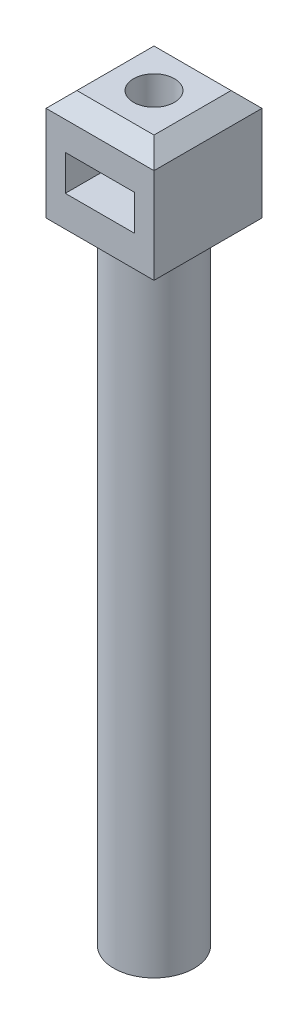
SolidWorks part; units mm, degrees
ref_plane "Front Plane" through (0, 0, 0) normal (0, 0, 1) x (1, 0, 0)
ref_plane "Top Plane" through (0, 0, 0) normal (0, 1, 0) x (1, 0, 0)
ref_plane "Right Plane" through (0, 0, 0) normal (1, 0, 0) x (0, 0, -1)
sketch "Sketch1" plane through (0, 0, 0) normal (0, 1, 0) x (1, 0, 0)
  circle A0 centre (0, 0) radius 6.604
  dimension "D1" = 13.208
extrude "Boss-Extrude1" add sketch "Sketch1" along normal blind 63.5
sketch "Sketch4" plane through (0, 0, 0) normal (0, -1, 0) x (1, 0, 0)
  line L1 (-12.7, -12.7) -> (12.7, -12.7)
  line L2 (-12.7, -12.7) -> (-12.7, 12.7)
  line L3 (-12.7, 12.7) -> (12.7, 12.7)
  line L4 (12.7, -12.7) -> (12.7, 12.7)
  line L5 (-12.7, -12.7) -> (12.7, 12.7) construction
  line L6 (-12.7, 12.7) -> (12.7, -12.7) construction
  point P0 (0, 0)
  dimension "D1" = 25.4
  dimension "D2" = 25.4
extrude "Boss-Extrude2" add sketch "Sketch4" along normal blind 1.27
ref_axis "Axis2" through (0, 63.5, 0) along (0, -1, 0)
ref_plane "Plane2" through (0, 50.8, 0) normal (0, 1, 0) x (1, 0, 0)
sketch "Sketch9" plane through (0, 50.8, 0) normal (0, 1, 0) x (1, 0, 0)
  line L1 (-8.89, -8.89) -> (8.89, -8.89)
  line L2 (-8.89, -8.89) -> (-8.89, 8.89)
  line L3 (-8.89, 8.89) -> (8.89, 8.89)
  line L4 (8.89, -8.89) -> (8.89, 8.89)
  line L5 (-8.89, -8.89) -> (8.89, 8.89) construction
  line L6 (-8.89, 8.89) -> (8.89, -8.89) construction
  point P0 (0, 0)
  dimension "D1" = 17.78
  dimension "D2" = 17.78
extrude "Boss-Extrude4" add sketch "Sketch9" along normal blind 20.32
sketch "Sketch10" plane through (0, 0, 8.89) normal (0, 0, 1) x (1, 0, 0)
  line L0 (0, 63.5) -> (0, 0) construction
  line L1 (-5.715, 58.039) -> (5.715, 58.039)
  line L2 (-5.715, 58.039) -> (-5.715, 63.881)
  line L3 (-5.715, 63.881) -> (5.715, 63.881)
  line L4 (5.715, 58.039) -> (5.715, 63.881)
  line L5 (-5.715, 58.039) -> (5.715, 63.881) construction
  line L6 (-5.715, 63.881) -> (5.715, 58.039) construction
  line L7 (-8.89, 71.12) -> (8.89, 71.12) construction
  line L8 (-8.89, 50.8) -> (8.89, 50.8) construction
  point P0 (0, 60.96)
  dimension "D1" = 11.43
  dimension "D2" = 5.842
  dimension "D3" = 7.239
  dimension "D4" = 7.239
extrude "Cut-Extrude2" cut sketch "Sketch10" against normal through all both and the other way through all
chamfer "Chamfer2" distance 2.54 angle 40 4 edges at (0, 50.8, -8.89) (-8.89, 50.8, 0) (8.89, 50.8, 0) (0, 50.8, 8.89) first distance on face at (0, 50.8, 0)
sketch "Sketch13" plane through (0, -1.27, 0) normal (0, -1, 0) x (1, 0, 0)
  line L1 (-12.7, 12.7) -> (12.7, 12.7)
  line L2 (-12.7, 12.7) -> (-12.7, -12.7)
  line L3 (-12.7, -12.7) -> (12.7, -12.7)
  line L4 (12.7, 12.7) -> (12.7, -12.7)
extrude "Cut-Extrude3" cut sketch "Sketch13" against normal blind 1.27
hole_wizard "1/4 Clearance Hole1" positions "Sketch16" profile "Sketch15" hole size "1/4" standard "ANSI Inch" end condition up to next
sketch "Sketch16" plane through (0, 71.12, 0) normal (0, 1, 0) x (1, 0, 0)
  point P0 (0, 0)
sketch "Sketch15" plane through (0, 71.12, 0) normal (1, 0, 0) x (0, 0, 1)
  line L0 (0, 0) -> (0, 7.239)
  line L1 (0, 7.239) -> (3.3782, 7.239)
  line L2 (3.3782, 7.239) -> (3.3782, 0)
  line L5 (3.3782, 0) -> (0, 0)
  line L11 (0, -6.35) -> (0, 107.95) construction
  dimension "Thru Hole Dia." = 6.7564
  dimension "Thru Hole Depth" = 7.239
chamfer "Chamfer3" distance 2.54 angle 45 1 edges at (8.89, 71.12, 0)
chamfer "Chamfer4" distance 2.54 angle 45 3 edges at (-1.27, 71.12, -8.89) (-8.89, 71.12, 0) (-1.27, 71.12, 8.89)
sketch "Sketch17" plane through (0, 0, 0) normal (0, -1, 0) x (1, 0, 0)
  circle A0 centre (0, 0) radius 6.604
extrude "Boss-Extrude5" add sketch "Sketch17" along normal blind 50.8
